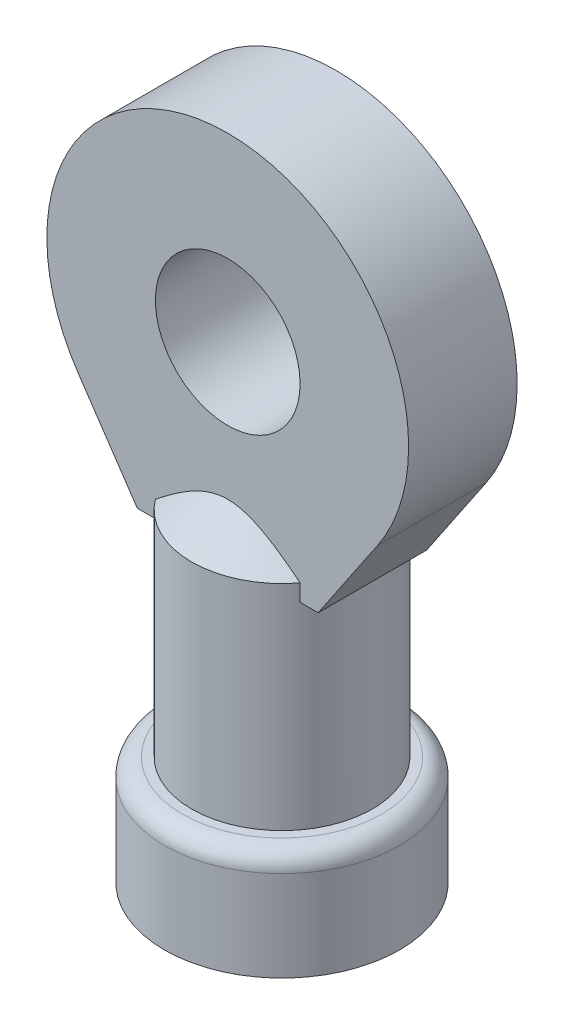
SolidWorks part; units mm, degrees
material "6063-T6"
ref_plane "Front Plane" through (0, 0, 0) normal (0, 0, 1) x (1, 0, 0)
ref_plane "Top Plane" through (0, 0, 0) normal (0, 1, 0) x (1, 0, 0)
ref_plane "Right Plane" through (0, 0, 0) normal (1, 0, 0) x (0, 0, -1)
sketch "Sketch1" plane through (0, 0, 0) normal (0, 1, 0) x (1, 0, 0)
  circle A0 centre (0, 0) radius 6.5
  dimension "D1" = 13
extrude "Boss-Extrude1" add sketch "Sketch1" along normal blind 6
fillet "Fillet1" radius 1 1 edges at (0, 6, 6.5)
sketch "Sketch3" plane through (0, 6, 0) normal (0, 1, 0) x (1, 0, 0)
  circle A0 centre (0, 0) radius 5
  dimension "D1" = 10
extrude "Boss-Extrude2" add sketch "Sketch3" along normal blind 13.83
sketch "Sketch2" plane through (0, 0, 0) normal (0, -1, 0) x (1, 0, 0)
  circle A0 centre (0, 0) radius 3
  dimension "D1" = 6
extrude "Cut-Extrude1" cut sketch "Sketch2" against normal blind 15
sketch "Sketch4" plane through (0, 0, 0) normal (0, 0, 1) x (1, 0, 0)
  line L0 (-5, 16.9) -> (-8.2863, 21.7644)
  line L1 (-5, 19.83) -> (-5, 6) construction
  line L2 (5, 16.9) -> (8.2863, 21.7644)
  line L3 (5, 6) -> (5, 19.83) construction
  line L7 (-5, 16.9) -> (5, 16.9)
  arc A0 (-8.2863, 21.7644) -> (8.2863, 21.7644) centre (0, 27.3624) cw
  circle A1 centre (0, 27.3624) radius 4
  dimension "D3" = 10
  dimension "D4" = 8
  dimension "D1" = 10.9
  dimension "D2" = 10.9
extrude "Boss-Extrude4" add sketch "Sketch4" along normal mid plane 6
ref_plane "Plane1" through (4, 19.83, -3) normal (-1, 0, 0) x (0, 0, 1)
chamfer "Chamfer2" distance 2 angle 45 2 edges at (0, 19.83, -5) (0, 19.83, 5)
